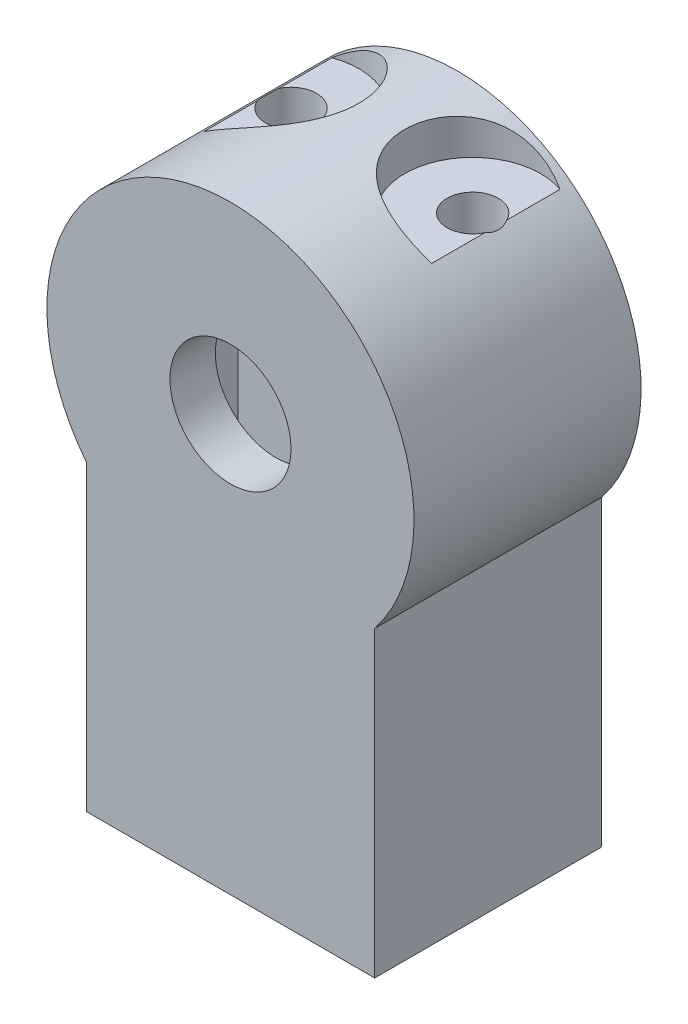
SolidWorks part; units mm, degrees
ref_plane "Front Plane" through (0, 0, 0) normal (0, 0, 1) x (1, 0, 0)
ref_plane "Top Plane" through (0, 0, 0) normal (0, 1, 0) x (1, 0, 0)
ref_plane "Right Plane" through (0, 0, 0) normal (1, 0, 0) x (0, 0, -1)
sketch "Sketch1" plane through (0, 0, 0) normal (0, 0, 1) x (1, 0, 0)
  line L0 (-19.05, -55) -> (19.05, -55)
  line L1 (19.05, -55) -> (19.05, -15)
  line L3 (-19.05, -55) -> (-19.05, -15)
  line L5 (0, -13.2) -> (0, 13.2) construction
  circle A0 centre (0, 0) radius 12
  arc A1 (-19.05, -15) -> (19.05, -15) centre (0, 0) cw
  point P9 (0, -55)
  dimension "D1" = 24
  dimension "D2" = 38.1
  dimension "D3" = 40
  dimension "D4" = 55
extrude "Boss-Extrude1" add sketch "Sketch1" along normal blind 7
sketch "Sketch2" plane through (0, 0, 0) normal (0, 0, 1) x (1, 0, 0)
  line L0 (-19.05, -55) -> (19.05, -55)
  line L1 (19.05, -55) -> (19.05, -15)
  line L3 (-19.05, -55) -> (-19.05, -15)
  circle A0 centre (0, 0) radius 8
  arc A1 (-19.05, -15) -> (19.05, -15) centre (0, 0) cw
  dimension "D1" = 16
  dimension "D2" = 38.1
  dimension "D3" = 40
  dimension "D4" = 55
extrude "Boss-Extrude2" add sketch "Sketch2" against normal blind 17
sketch "Sketch3" plane through (0, 0, 0) normal (0, 1, 0) x (1, 0, 0)
  line L0 (-12, 7) -> (12, 7) construction
  line L1 (0, -13.2) -> (0, 13.2) construction
  circle A0 centre (-12, 7) radius 3.38
  circle A1 centre (12, 7) radius 3.38
  point P4 (0, 7)
  dimension "D1" = 24
  dimension "D2" = 6.76
  dimension "D3" = 6.76
  dimension "D4" = 7
extrude "Cut-Extrude1" cut sketch "Sketch3" against normal through all both and the other way through all
sketch "Sketch4" plane through (0, 0, 0) normal (0, 1, 0) x (1, 0, 0)
  circle A0 centre (-12, 7) radius 9
  circle A1 centre (12, 7) radius 9
  dimension "D1" = 18
extrude "Cut-Extrude2" cut sketch "Sketch4" against normal blind 17 from offset 36
sketch "Sketch5" plane through (0, 0, 0) normal (0, 0, 1) x (1, 0, 0)
  line L0 (13.2, 0) -> (-13.2, 0) construction
  line L1 (-12, 0) -> (12, 0)
  line L2 (-12, 0) -> (-12, -55)
  line L3 (-12, -55) -> (12, -55)
  line L4 (12, 0) -> (12, -55)
  line L5 (0, -13.2) -> (0, 13.2) construction
  line L6 (-19.05, -55) -> (19.05, -55) construction
  point P6 (0, 0)
  dimension "D1" = 24
extrude "Cut-Extrude3" cut sketch "Sketch5" along normal blind 7
extrude "Boss-Extrude4" add sketch "Sketch2<2>" along normal blind 6 from offset 7
sketch "Sketch2<2>" plane through (0, 0, 0) normal (0, 0, 1) x (1, 0, 0) same geometry as "Sketch2"
equation "\"bearingOuterDiameter\"= 24mm"
equation "\"bearingDepth\"= 7mm"
equation "\"holeDiameter\"= 6.76mm"
equation "\"D1@Sketch1\"=\"bearingOuterDiameter\""
equation "\"D2@Sketch1\"=25.4*1.5"
equation "\"D1@Boss-Extrude1\"=\"bearingDepth\""
equation "\"D2@Sketch3\"=\"holeDiameter\""
equation "\"D3@Sketch3\"=\"holeDiameter\""
equation "\"D1@Sketch5\"=\"bearingOuterDiameter\""
equation "\"D1@Cut-Extrude3\"=\"bearingDepth\""
